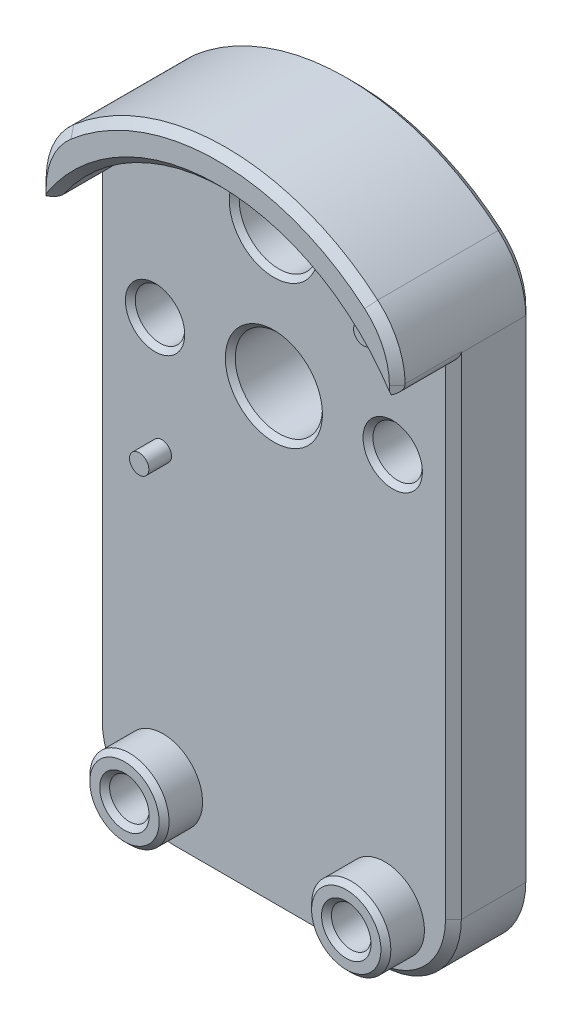
SolidWorks part; units mm, degrees
material "Onyx"
ref_plane "Front" through (0, 0, 0) normal (0, 0, 1) x (1, 0, 0)
ref_plane "Top" through (0, 0, 0) normal (0, 1, 0) x (1, 0, 0)
ref_plane "Right" through (0, 0, 0) normal (1, 0, 0) x (0, 0, -1)
sketch "Sketch2" plane through (0, 0, 0) normal (0, 0, 1) x (1, 0, 0)
  line L0 (0, 15.3416) -> (0, -36.5125) construction
  line L1 (14.3891, -36.5125) -> (-14.3891, -36.5125)
  line L2 (14.3891, -36.5125) -> (14.3891, 11.7424)
  line L4 (-14.3891, -36.5125) -> (-14.3891, 11.7424)
  line L5 (-15.4933, 0) -> (15.4933, 0) construction
  line L6 (-14.3891, 15.3416) -> (14.3891, 15.3416) construction
  line L8 (-14.3891, -28.0416) -> (14.3891, -28.0416) construction
  line L9 (-14.3891, -31.8516) -> (14.3891, -31.8516) construction
  line L10 (-8.89, 15.3416) -> (-8.89, -31.8516) construction
  line L11 (8.89, 15.3416) -> (8.89, -31.8516) construction
  circle A1 centre (0, 0) radius 3.4925
  arc A2 (-15.4933, 0) -> (15.4933, 0) centre (0, -0.1524) cw construction
  arc A7 (-14.3891, 11.7424) -> (14.3891, 11.7424) centre (0, -0.1524) cw
  arc A8 (-18.6681, 0.0312) -> (18.6681, 0.0312) centre (0, -0.1524) cw construction
  point P10 (0, 0)
  dimension "D4" = 6.985
  dimension "D2" = 15.494
  dimension "D1" = 28.7782
  dimension "D3" = 15.3416
  dimension "D8" = 5.4991
  dimension "D9" = 5.4991
  dimension "D5" = 43.3832
  dimension "D11" = 3.81
  dimension "D12" = 4.6609
  dimension "D6" = 3.175
extrude "Boss-Extrude1" add sketch "Sketch2" along normal blind 6.4375
sketch "Sketch12" plane through (0, 0, 6.4375) normal (0, 0, 1) x (1, 0, 0)
  line L2 (-14.3891, 6.2471) -> (-14.3891, 11.7424)
  line L3 (14.3891, 11.7424) -> (14.3891, 6.2471)
  arc A0 (15.4933, 0) -> (-15.4933, 0) centre (0, -0.1524) ccw construction
  arc A1 (15.4933, 0) -> (-15.4933, 0) centre (0, -0.1524) ccw construction
  arc A3 (-14.3891, 11.7424) -> (14.3891, 11.7424) centre (0, -0.1524) cw
  arc A4 (14.3891, 11.7424) -> (-14.3891, 11.7424) centre (0, -0.1524) ccw construction
  arc A5 (-14.3891, 6.2471) -> (14.3891, 6.2471) centre (0, -0.1524) cw
  dimension "D1" = 0.254
extrude "Boss-Extrude5" add sketch "Sketch12" along normal blind 4.4958
sketch "Sketch17" plane through (0, 0, 6.4375) normal (0, 0, 1) x (1, 0, 0)
  line L0 (-20.1442, 0) -> (18.28, 0) construction
  circle A0 centre (0, 0) radius 9.525 construction
  circle A1 centre (-9.525, 0) radius 1.9812
  circle A2 centre (9.525, 0) radius 1.9812
  dimension "D1" = 19.05
  dimension "D2" = 3.9624
extrude "Cut-Extrude7" cut sketch "Sketch17" against normal up to next
sketch "Sketch11" plane through (0, 0, 0) normal (0, 0, -1) x (-1, 0, 0)
  line L0 (14.3891, 11.7424) -> (14.3891, -36.5125) construction
  line L1 (9.525, -3.3729) -> (12.446, -1.6864)
  line L2 (12.446, -1.6864) -> (12.446, 1.6864)
  line L3 (12.446, 1.6864) -> (9.525, 3.3729)
  line L4 (9.525, 3.3729) -> (6.604, 1.6864)
  line L5 (6.604, 1.6864) -> (6.604, -1.6864)
  line L6 (6.604, -1.6864) -> (9.525, -3.3729)
  line L7 (-14.3891, -36.5125) -> (-14.3891, 11.7424) construction
  line L8 (-6.604, -1.6864) -> (-6.604, 1.6864)
  line L9 (-6.604, 1.6864) -> (-9.525, 3.3729)
  line L10 (-9.525, 3.3729) -> (-12.446, 1.6864)
  line L11 (-12.446, 1.6864) -> (-12.446, -1.6864)
  line L12 (-12.446, -1.6864) -> (-9.525, -3.3729)
  line L13 (-9.525, -3.3729) -> (-6.604, -1.6864)
  circle A0 centre (9.525, 0) radius 2.921 construction
  circle A1 centre (-9.525, 0) radius 2.921 construction
  dimension "D1" = 5.842
sketch "Sketch13" plane through (0, 0, 6.4375) normal (0, 0, 1) x (1, 0, 0)
  line L0 (0, 0) -> (0, -36.5125) construction
  line L1 (-14.3891, -36.5125) -> (14.3891, -36.5125) construction
  line L2 (8.89, -31.75) -> (-8.89, -31.75) construction
  circle A1 centre (8.89, -31.75) radius 1.5875
  circle A2 centre (-8.89, -31.75) radius 1.5875
  point P9 (0, -31.75)
  dimension "D1" = 3.175
  dimension "D3" = 8.89
  dimension "D2" = 4.7625
extrude "Cut-Extrude5" cut sketch "Sketch13" against normal through all
ref_axis "Axis1" through (0, 0, 36.4243) along (0, 0, -1)
sketch "Sketch7" plane through (0, 0, 0) normal (0, 0, -1) x (-1, 0, 0)
  line L0 (0, 18.5166) -> (0, -36.5125) construction
  line L2 (14.3891, -36.5125) -> (-14.3891, -36.5125) construction
  line L3 (-14.3891, -15.875) -> (14.3891, -15.875) construction
  line L4 (14.3891, 6.2471) -> (14.3891, -36.5125) construction
  circle A0 centre (0, -15.875) radius 3.9688
  arc A1 (14.3891, -12.0472) -> (-14.3891, -12.0472) centre (0, -0.1524) ccw construction
  dimension "D1" = 7.9375
  dimension "D2" = 15.875
extrude "Boss-Extrude4" add sketch "Sketch7" along normal blind 3.175
sketch "Sketch14" plane through (0, 0, 0) normal (0, 0, -1) x (-1, 0, 0)
  line L0 (0, 0) -> (0, 18.5166) construction
  arc A0 (14.3891, 11.7424) -> (-14.3891, 11.7424) centre (0, -0.1524) ccw construction
  circle A1 centre (0, 11.1125) radius 3.175
  dimension "D1" = 6.35
  dimension "D2" = 11.1125
extrude "Cut-Extrude6" cut sketch "Sketch14" against normal through all
sketch "Sketch15" plane through (0, 0, 6.4375) normal (0, 0, 1) x (1, 0, 0)
  circle A0 centre (-8.89, -31.75) radius 3.175
  circle A1 centre (-8.89, -31.75) radius 1.5875 construction
  circle A2 centre (8.89, -31.75) radius 3.175
  circle A3 centre (8.89, -31.75) radius 1.5875 construction
  circle A4 centre (8.89, -31.75) radius 1.5875
  circle A5 centre (-8.89, -31.75) radius 1.5875
  dimension "D1" = 1.5875
extrude "Boss-Extrude7" add sketch "Sketch15" along normal blind 3.0875
sketch "Sketch16" plane through (0, 0, 0) normal (0, 0, 1) x (1, 0, 0)
  line L10 (-14.3891, 6.2471) -> (-14.3891, -36.5125) construction
  line L11 (-14.3891, -36.5125) -> (14.3891, -36.5125) construction
  line L12 (14.3891, -36.5125) -> (14.3891, 6.2471) construction
  circle A0 centre (8.98, 8.98) radius 0.7747
  circle A1 centre (-8.98, -8.98) radius 0.7747
  dimension "D1" = 1.5494
  dimension "D4" = 5.4091
  dimension "D2" = 5.4091
  dimension "D3" = 27.5325
  dimension "D5" = 45.4925
extrude "Boss-Extrude8" add sketch "Sketch16" along normal blind 8.255
extrude "Cut-Extrude8" cut sketch "Sketch11" against normal blind 2.8448
chamfer "Chamfer1" distance 0.3969 angle 45 25 edges at (-3.175, 11.1125, 6.4375) (-3.175, 11.1125, 0) (3.4925, 0, 0) (3.4925, 0, 6.4375) (-3.9688, -15.875, -3.175) (-10.9855, -2.5297, 0) (-8.0645, -2.5297, 0) (-6.604, 0, 0) (-8.0645, 2.5297, 0) (-10.9855, 2.5297, 0) (-12.446, 0, 0) (-7.5438, 0, 6.4375) (11.5062, 0, 6.4375) (8.0645, 2.5297, 0) (10.9855, 2.5297, 0) (12.446, 0, 0) (10.9855, -2.5297, 0) (8.0645, -2.5297, 0) (6.604, 0, 0) (-5.715, -31.75, 9.525) (-7.3025, -31.75, 9.525) (10.4775, -31.75, 9.525) (12.065, -31.75, 9.525) (-7.3025, -31.75, 0) (10.4775, -31.75, 0)
fillet "Fillet1" radius 6.35 4 edges at (14.3891, -36.5125, 3.2188) (-14.3891, -36.5125, 3.2188) (-14.3891, 11.7424, 5.4667) (14.3891, 11.7424, 5.4667)
chamfer "Chamfer2" distance 0.635 angle 45 19 edges at (13.8113, 11.8286, 10.9333) (14.3891, 7.7145, 10.9333) (0, 15.5956, 10.9333) (-14.3891, 7.7145, 10.9333) (-13.8113, 11.8286, 10.9333) (0, 18.5166, 10.9333) (13.8113, 11.8286, 0) (14.3891, -10.4903, 0) (0, 18.5166, 0) (12.5292, -34.6526, 0) (-13.8113, 11.8286, 0) (0, -36.5125, 0) (-14.3891, -10.4903, 0) (-12.5292, -34.6526, 0) (-14.3891, -11.9577, 6.4375) (14.3891, -11.9577, 6.4375) (-12.5292, -34.6526, 6.4375) (12.5292, -34.6526, 6.4375) (0, -36.5125, 6.4375)
fillet "Fillet2" radius 0.7937 2 edges at (-14.3891, 6.2471, 8.0504) (14.3891, 6.2471, 8.0504)
equation "\"D1@Boss-Extrude5\"=0.354/2"
equation "\"D2@Sketch7\"=1.25/2"
equation "\"D11@Sketch2\"=0.15000000"
equation "\"D12@Sketch2\"=0.1210000+0.0625"
